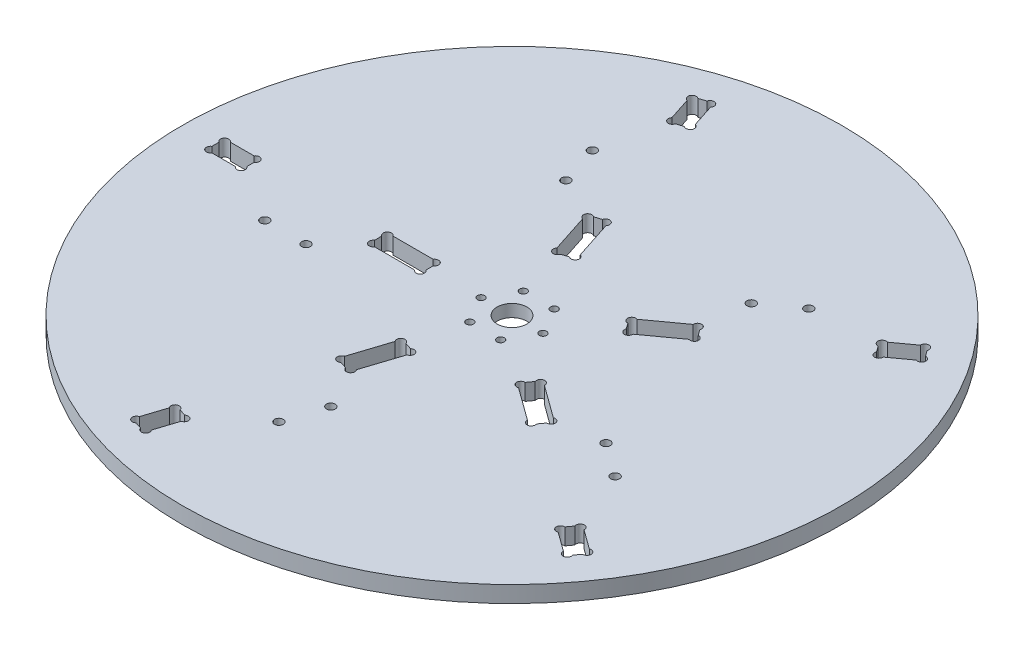
SolidWorks part; units mm, degrees
material "PE High Density"
ref_plane "Front Plane" through (0, 0, 0) normal (0, 0, 1) x (1, 0, 0)
ref_plane "Top Plane" through (0, 0, 0) normal (0, 1, 0) x (1, 0, 0)
ref_plane "Right Plane" through (0, 0, 0) normal (1, 0, 0) x (0, 0, -1)
sketch "Sketch1" plane through (0, 0, 0) normal (0, 1, 0) x (1, 0, 0)
  circle A0 centre (0, 0) radius 254
  dimension "D1" = 508
extrude "Boss-Extrude1" add sketch "Sketch1" along normal mid plane 12.7
sketch "Sketch12" plane through (0, 6.35, 0) normal (0, 1, 0) x (1, 0, 0)
  line L0 (23.8125, 0) -> (11.9063, -20.6222) construction
  line L1 (11.9063, -20.6222) -> (-11.9063, -20.6222) construction
  line L2 (-11.9063, -20.6222) -> (-23.8125, 0) construction
  line L3 (-23.8125, 0) -> (-11.9063, 20.6222) construction
  line L4 (-11.9063, 20.6222) -> (11.9063, 20.6222) construction
  line L5 (11.9063, 20.6222) -> (23.8125, 0) construction
  line L6 (23.8125, 0) -> (0, 0) construction
  line L7 (0, 0) -> (11.9063, 20.6222) construction
  circle A0 centre (0, 0) radius 11.43
  circle A1 centre (0, 0) radius 23.8125 construction
  circle A2 centre (0, 0) radius 29.337 construction
  point P4 (23.8125, 0)
  point P5 (-23.8125, 0)
  point P6 (-11.9063, 20.6222)
  point P7 (11.9063, 20.6222)
  point P8 (-11.9063, -20.6222)
  point P9 (11.9063, -20.6222)
  dimension "D1" = 22.86
  dimension "D2" = 47.625
  dimension "D3" = 58.674
hole_wizard "#10 Clearance Hole1" positions "Sketch13" profile "Sketch14" hole size "#10" standard "ANSI Inch" end condition up to next
sketch "Sketch13" plane through (0, 6.35, 0) normal (0, 1, 0) x (1, 0, 0)
  point P0 (-11.9063, 20.6222)
  point P3 (11.9063, 20.6222)
  point P6 (23.8125, 0)
  point P9 (11.9063, -20.6222)
  point P12 (-11.9063, -20.6222)
  point P15 (-23.8125, 0)
sketch "Sketch14" plane through (-11.9063, 6.35, -20.6222) normal (1, 0, 0) x (0, 0, 1)
  line L0 (0, 0) -> (0, 12.7)
  line L1 (0, 12.7) -> (2.8067, 12.7)
  line L2 (2.8067, 12.7) -> (2.8067, 0)
  line L5 (2.8067, 0) -> (0, 0)
  line L11 (0, -6.35) -> (0, 107.95) construction
  dimension "Thru Hole Dia." = 5.6134
  dimension "Thru Hole Depth" = 12.7
sketch "Sketch3" plane through (0, 6.35, 0) normal (0, 1, 0) x (1, 0, 0)
  line L0 (0, 0) -> (-50000, 0) construction
  line L1 (-254, -3.175) -> (-254, -50003.175) construction
  line L2 (-103.1875, 7.1437) -> (-63.5, 7.1437)
  line L3 (-103.1875, 7.1437) -> (-103.1875, -7.1438)
  line L4 (-103.1875, -7.1438) -> (-63.5, -7.1437)
  line L5 (-63.5, 7.1437) -> (-63.5, -7.1437)
  line L6 (-103.1875, 7.1437) -> (-63.5, -7.1437) construction
  line L7 (-103.1875, -7.1438) -> (-63.5, 7.1437) construction
  line L8 (-228.6, 7.1437) -> (-201.6125, 7.1437)
  line L9 (-228.6, 7.1437) -> (-228.6, -7.1437)
  line L10 (-228.6, -7.1437) -> (-201.6125, -7.1437)
  line L11 (-201.6125, 7.1437) -> (-201.6125, -7.1437)
  line L12 (-228.6, 7.1437) -> (-201.6125, -7.1437) construction
  line L13 (-228.6, -7.1437) -> (-201.6125, 7.1437) construction
  line L14 (-38.1, -3.175) -> (-38.1, -50003.175) construction
  line L16 (-202.4062, -6.35) -> (-227.8062, -6.35) construction
  line L17 (-202.4062, -6.35) -> (-202.4062, 6.35) construction
  line L18 (-202.4062, 6.35) -> (-227.8062, 6.35) construction
  line L19 (-227.8062, -6.35) -> (-227.8062, 6.35) construction
  line L20 (-202.4062, -6.35) -> (-227.8062, 6.35) construction
  line L21 (-202.4062, 6.35) -> (-227.8062, -6.35) construction
  line L22 (-64.2938, -6.35) -> (-102.3938, -6.35) construction
  line L23 (-64.2938, -6.35) -> (-64.2938, 6.35) construction
  line L24 (-64.2938, 6.35) -> (-102.3938, 6.35) construction
  line L25 (-102.3938, -6.35) -> (-102.3938, 6.35) construction
  line L26 (-64.2938, -6.35) -> (-102.3938, 6.35) construction
  line L27 (-64.2938, 6.35) -> (-102.3938, -6.35) construction
  circle A0 centre (0, 0) radius 38.1 construction
  circle A1 centre (0, 0) radius 254 construction
  point P3 (-83.3438, 0)
  point P10 (-215.1062, 0)
  point P21 (-215.1062, 0)
  point P26 (-83.3438, 0)
  dimension "D1" = 76.2
  dimension "D2" = 14.2875
  dimension "D3" = 26.9875
  dimension "D4" = 25.4
  dimension "D5" = 25.4
  dimension "D6" = 39.6875
  dimension "D7" = 12.7
  dimension "D8" = 25.4
  dimension "D9" = 38.1
extrude "Cut-Extrude2" cut sketch "Sketch3" against normal through all
sketch "Sketch22" plane through (0, 6.35, 0) normal (0, 1, 0) x (1, 0, 0)
  line L0 (-202.4062, -6.35) -> (-102.3938, -6.35) construction
  line L1 (-158.75, -31.75) -> (-127, -31.75) construction
  line L2 (-38.1, 199996.825) -> (-38.1, -250003.175) construction
  line L3 (-171.45, -6.35) -> (-114.3, -6.35) construction
  line L4 (-171.45, -6.35) -> (-171.45, -44.45) construction
  line L5 (-171.45, -44.45) -> (-114.3, -44.45) construction
  line L6 (-114.3, -6.35) -> (-114.3, -44.45) construction
  line L7 (-142.875, -31.75) -> (-142.875, -44.45) construction
  dimension "D1" = 31.75
  dimension "D2" = 25.4
  dimension "D3" = 76.2
  dimension "D4" = 38.1
  dimension "D5" = 57.15
hole_wizard "1/4 Clearance Hole1" positions "Sketch23" profile "Sketch24" hole size "1/4" standard "ANSI Inch" end condition through all
sketch "Sketch23" plane through (0, 6.35, 0) normal (0, 1, 0) x (1, 0, 0)
  point P0 (-158.75, -31.75)
  point P3 (-127, -31.75)
sketch "Sketch24" plane through (-158.75, 6.35, 31.75) normal (1, 0, 0) x (0, 0, 1)
  line L0 (0, 0) -> (0, 12.7)
  line L1 (0, 12.7) -> (3.3782, 12.7)
  line L2 (3.3782, 12.7) -> (3.3782, 0)
  line L5 (3.3782, 0) -> (0, 0)
  line L11 (0, -6.35) -> (0, 107.95) construction
  dimension "Thru Hole Dia." = 6.7564
  dimension "Thru Hole Depth" = 12.7
ref_axis "Axis1" through (0, 10.4775, 0) along (0, -1, 0)
sketch "Sketch25" plane through (0, 6.35, 0) normal (0, 1, 0) x (1, 0, 0)
  line L0 (-225.2324, 7.1437) -> (-228.6, 3.7762) construction
  line L1 (-201.6125, 7.1437) -> (-228.6, 7.1437) construction
  line L2 (-228.6, 7.1437) -> (-228.6, -7.1437) construction
  line L3 (-228.6, 7.1438) -> (-225.2324, 3.7762) construction
  line L4 (-99.8199, 7.1437) -> (-103.1875, 3.7762) construction
  line L5 (-203.2963, -5.46) -> (-226.9162, -5.46) construction
  line L6 (-203.2963, -5.46) -> (-203.2963, 5.46) construction
  line L7 (-203.2963, 5.46) -> (-226.9162, 5.46) construction
  line L8 (-226.9162, -5.46) -> (-226.9162, 5.46) construction
  line L9 (-203.2963, -5.46) -> (-226.9162, 5.46) construction
  line L10 (-203.2963, 5.46) -> (-226.9162, -5.46) construction
  line L11 (-65.1838, -5.46) -> (-101.5037, -5.46) construction
  line L12 (-65.1838, -5.46) -> (-65.1838, 5.46) construction
  line L13 (-65.1838, 5.46) -> (-101.5037, 5.46) construction
  line L14 (-101.5037, -5.46) -> (-101.5037, 5.46) construction
  line L15 (-65.1838, -5.46) -> (-101.5037, 5.46) construction
  line L16 (-65.1838, 5.46) -> (-101.5037, -5.46) construction
  line L17 (-99.8199, 3.7762) -> (-103.1875, 7.1437) construction
  line L18 (-63.5, 7.1437) -> (-103.1875, 7.1437) construction
  circle A0 centre (-226.9162, 5.46) radius 2.3813 construction
  circle A1 centre (-101.5037, 5.46) radius 2.3813 construction
  point P4 (-226.9162, 5.46)
  point P5 (-83.3438, 0)
  point P8 (-215.1062, 0)
  point P13 (-226.9162, 5.46)
  point P27 (-101.5037, 5.46)
  point P30 (-101.5037, 5.46)
  dimension "D1" = 4.7625
hole_wizard "1/4 (0.2500) Dowel Hole2" positions "Sketch17" profile "Sketch18" hole size "1/4" standard "ANSI Inch" end condition through all
sketch "Sketch17" plane through (0, 6.35, 0) normal (0, 1, 0) x (1, 0, 0)
  point P24 (-65.1838, 5.46)
  point P26 (-65.1838, -5.46)
  point P28 (-101.5037, -5.46)
  point P30 (-101.5037, 5.46)
  point P32 (-203.2963, 5.46)
  point P34 (-203.2963, -5.46)
  point P36 (-226.9162, -5.46)
  point P38 (-226.9162, 5.46)
sketch "Sketch18" plane through (-65.1838, 6.35, -5.46) normal (1, 0, 0) x (0, 0, 1)
  line L0 (0, 0) -> (0, 12.7)
  line L1 (0, 12.7) -> (3.175, 12.7)
  line L2 (3.175, 12.7) -> (3.175, 0)
  line L5 (3.175, 0) -> (0, 0)
  line L11 (0, -6.35) -> (0, 107.95) construction
  dimension "Thru Hole Dia." = 6.35
  dimension "Thru Hole Depth" = 12.7
pattern_circular "CirPattern1" count 5 over 360 about axis through (0, 10.4775, 0) along (0, -1, 0) of "Cut-Extrude2", "1/4 (0.2500) Dowel Hole2", "1/4 Clearance Hole1"
hole_wizard "CBORE for 1/4 Hex Head Bolt1" positions "Sketch28" profile "Sketch29" counterbore size "1/4" standard "ANSI Inch" end condition through all
sketch "Sketch28" plane through (0, -6.35, 0) normal (0, 1, 0) x (1, 0, 0)
  point P0 (0, 0)
sketch "Sketch29" plane through (0, -6.35, 0) normal (1, 0, 0) x (0, 0, -1)
  line L0 (0, 0) -> (0, 12.7)
  line L1 (0, 12.7) -> (11.43, 12.7)
  line L3 (11.43, 12.7) -> (11.43, 3.175)
  line L4 (11.43, 3.175) -> (15.875, 3.175)
  line L5 (15.875, 3.175) -> (15.875, 0)
  line L7 (15.875, 0) -> (0, 0)
  line L11 (0, -6.35) -> (0, 107.95) construction
  dimension "Thru Hole Dia." = 22.86
  dimension "Thru Hole Depth" = 12.7
  dimension "C'Bore Dia." = 31.75
  dimension "C'Bore Depth" = 3.175
